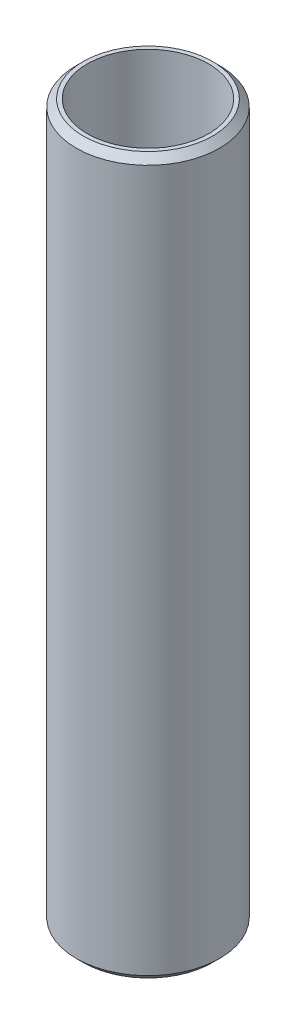
SolidWorks part; units mm, degrees
ref_plane "Front Plane" through (0, 0, 0) normal (0, 0, 1) x (1, 0, 0)
ref_plane "Top Plane" through (0, 0, 0) normal (0, 1, 0) x (1, 0, 0)
ref_plane "Right Plane" through (0, 0, 0) normal (1, 0, 0) x (0, 0, -1)
sketch "Sketch1" plane through (0, 0, 0) normal (0, 1, 0) x (1, 0, 0)
  circle A0 centre (0, 0) radius 55
  dimension "SHAFT_OD" = 110
extrude "Boss-Extrude1" add sketch "Sketch1" along normal blind 549.5256
sketch "Sketch2" plane through (0, 0, 0) normal (0, 1, 0) x (1, 0, 0)
  circle A0 centre (0, 0) radius 46.5483
  dimension "BORE_D" = 93.0966
extrude "Cut-Extrude1" cut sketch "Sketch2" along normal through all
chamfer "Chamfer1" distance 5.3697 angle 45 2 edges at (0, 549.5256, 55) (0, 0, 55)
